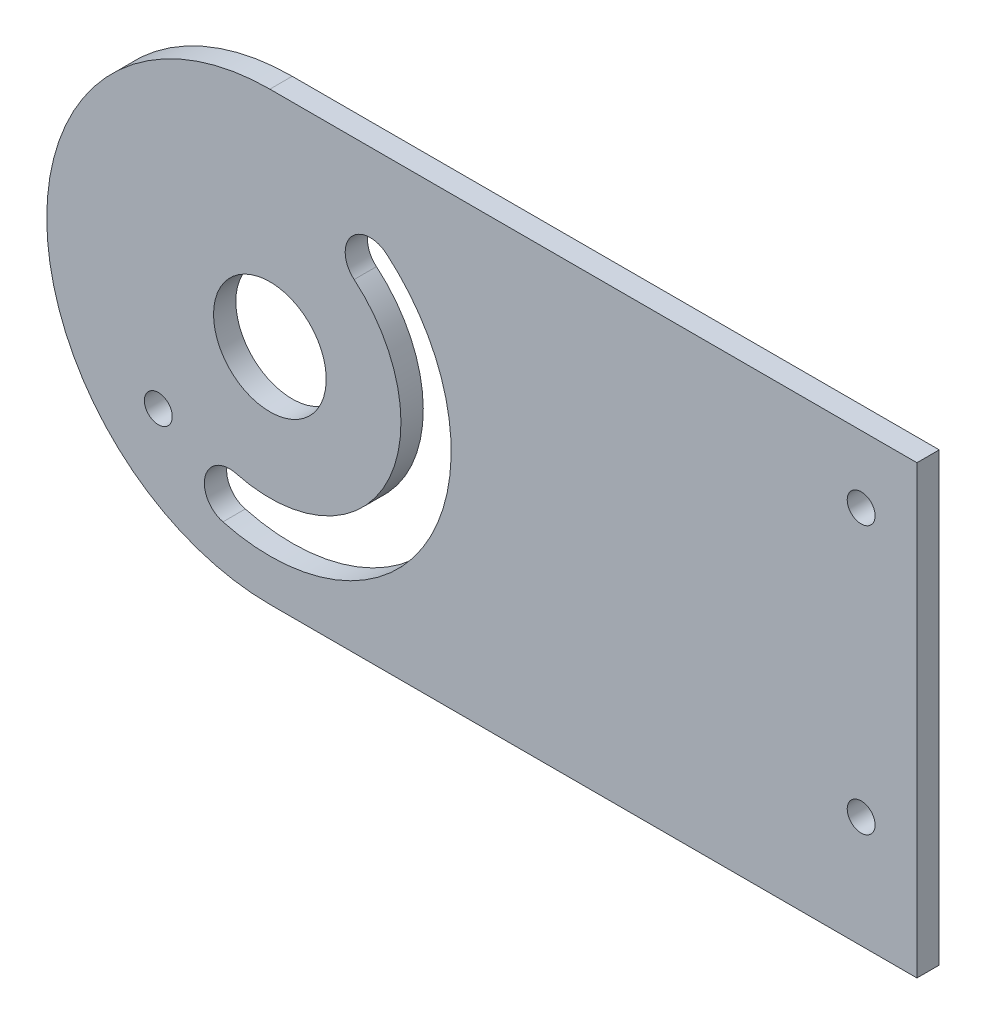
SolidWorks part; units mm, degrees
ref_plane "前视基准面" through (0, 0, 0) normal (0, 0, 1) x (1, 0, 0)
ref_plane "上视基准面" through (0, 0, 0) normal (0, 1, 0) x (1, 0, 0)
ref_plane "右视基准面" through (0, 0, 0) normal (1, 0, 0) x (0, 0, -1)
other "Configuration Table"
sketch "草图2" plane through (0, 0, 0) normal (0, 0, 1) x (1, 0, 0)
  line L0 (0, 0) -> (0, 40)
  line L1 (0, 40) -> (78, 40)
  line L2 (78, 40) -> (78, 0)
  line L3 (78, 0) -> (0, 0)
  dimension "D1" = 40
  dimension "D2" = 78
extrude "凸台-拉伸1" add sketch "草图2" along normal blind 2
sketch "草图3" plane through (0, 0, 0) normal (0, 0, -1) x (-1, 0, 0)
  line L5 (-76, 40) -> (-76, 0) construction
  line L6 (-78, 40) -> (0, 40) construction
  line L7 (-20, 20) -> (-29, 30.7238) construction
  line L8 (-20, 20) -> (-16.3753, 6.4774) construction
  circle A0 centre (-20, 20) radius 5.05
  circle A1 centre (-20, 20) radius 14 construction
  arc A3 (-29, 30.7238) -> (-16.3753, 6.4774) centre (-20, 20) ccw construction
  arc A4 (-30.4464, 32.4473) -> (-15.7928, 4.3041) centre (-20, 20) ccw
  arc A5 (-27.5536, 29.0003) -> (-16.9578, 8.6506) centre (-20, 20) ccw
  arc A6 (-27.5536, 29.0003) -> (-30.4464, 32.4473) centre (-29, 30.7238) ccw
  arc A7 (-15.7928, 4.3041) -> (-16.9578, 8.6506) centre (-16.3753, 6.4774) ccw
  circle A8 centre (-10, 10.202) radius 1.25
  point P13 (-32.4176, 13.5344)
  dimension "D1" = 10.1
  dimension "D4" = 28
  dimension "D5" = 20
  dimension "D8" = 4.5
  dimension "D9" = 2.5
  dimension "D3" = 56
  dimension "D6" = 155
  dimension "D7" = 9
  dimension "D10" = 10
extrude "切除-拉伸1" cut sketch "草图3" against normal through all
sketch "草图4" plane through (0, 0, 0) normal (0, 0, -1) x (-1, 0, 0)
  line L0 (-78, 0) -> (-78, 40) construction
  line L1 (0, 0) -> (-78, 0) construction
  line L2 (-78, 40) -> (0, 40) construction
  circle A0 centre (-73, 34) radius 1.25
  circle A1 centre (-73, 10) radius 1.25
  dimension "D1" = 2.5
  dimension "D2" = 5
  dimension "D3" = 10
  dimension "D4" = 6
extrude "切除-拉伸2" cut sketch "草图4" against normal through all
fillet "圆角1" radius 20 2 edges at (0, 40, 1) (0, 0, 1)
hole_wizard "M3 螺纹孔的螺纹孔钻头1" positions "3D草图2" profile "草图6" hole size "M3" standard "GB" end condition through all
sketch3d "3D草图2"
  line L0 (73, 34, 2) -> (73, 34, 0) construction
  line L1 (73, 10, 2) -> (73, 10, 0) construction
  point P0 (73, 34, 0)
  point P4 (73, 10, 0)
sketch "草图6" plane through (73, 34, 0) normal (1, 0, 0) x (0, 1, 0)
  line L0 (0, 0) -> (0, 2)
  line L1 (0, 2) -> (1.25, 2)
  line L2 (1.25, 2) -> (1.25, 0.025)
  line L3 (1.25, 0.025) -> (1.275, 0)
  line L5 (1.275, 0) -> (0, 0)
  line L6 (-1.25, 0.025) -> (-1.275, 0) construction
  line L11 (0, -6.35) -> (0, 107.95) construction
  dimension "通孔孔直径" = 2.5
  dimension "通孔孔深度" = 2
  dimension "近端锥形沉头孔直径" = 2.55
  dimension "近端锥形沉头孔角度" = 90
